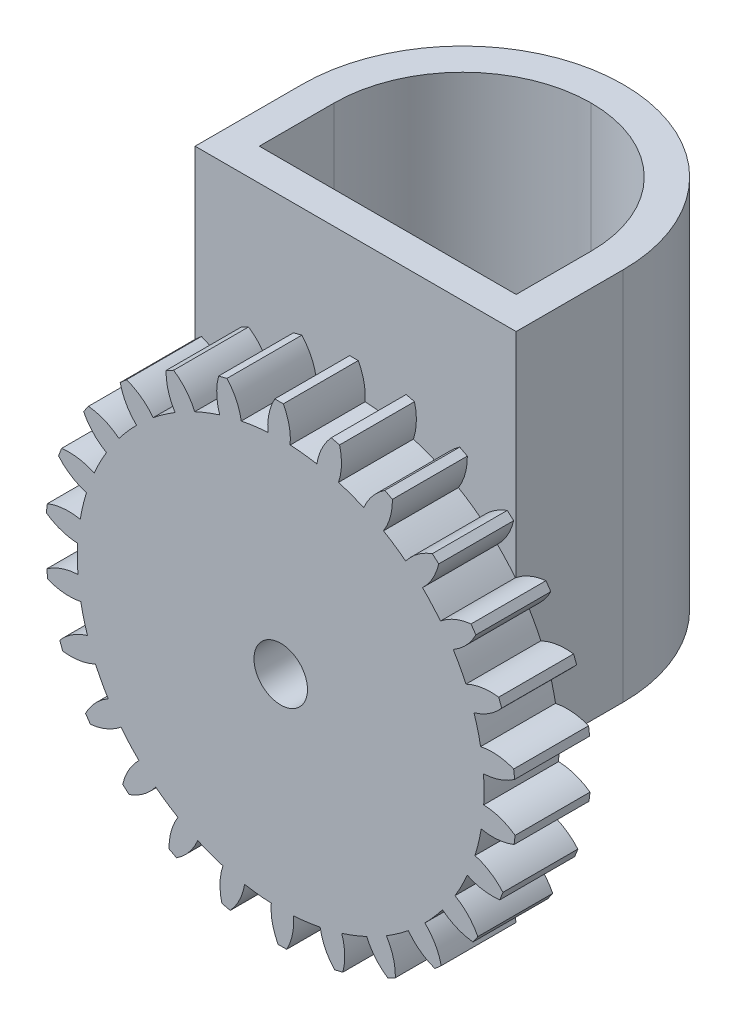
SolidWorks part; units mm, degrees
note: The reader was unsure of these and kept them because the rebuilt part matched: shared geometry of "Sketch5<8>".
ref_plane "Front Plane" through (0, 0, 0) normal (0, 0, 1) x (1, 0, 0)
ref_plane "Top Plane" through (0, 0, 0) normal (0, 1, 0) x (1, 0, 0)
ref_plane "Right Plane" through (0, 0, 0) normal (1, 0, 0) x (0, 0, -1)
sketch "Sketch4" plane through (0, 0, 0) normal (0, 1, 0) x (1, 0, 0)
  line L1 (15, 12.5) -> (-15, 12.5)
  line L2 (15, 12.5) -> (15, -12.5)
  line L3 (15, -12.5) -> (-15, -12.5)
  line L4 (-15, 12.5) -> (-15, -12.5)
  line L5 (15, 12.5) -> (-15, -12.5) construction
  line L6 (15, -12.5) -> (-15, 12.5) construction
  point P0 (0, 0)
  dimension "D1" = 25
  dimension "D2" = 30
extrude "Boss-Extrude2" add sketch "Sketch4" against normal blind 35
fillet "Fillet1" radius 15 2 edges at (-15, -17.5, -12.5) (15, -17.5, -12.5)
shell "Shell1" thickness 3
sketch "Sketch5" plane through (0, 0, 12.5) normal (0, 0, 1) x (1, 0, 0)
  line L1 (-0.2425, -53.7182) -> (0.5575, -53.7182)
  line L2 (0, -50.7232) -> (1.197, -50.6854)
  circle A1 centre (0, -31.7232) radius 19
  arc A3 (0.5575, -53.7182) -> (1.197, -50.6854) centre (-4.1843, -51.1345) ccw
  arc A4 (-0.2425, -53.7182) -> (-0.882, -50.6854) centre (4.4993, -51.1345) cw
  dimension "D2" = 38
extrude "Boss-Extrude5" add sketch "Sketch5" along normal blind 7 contours A1
extrude "Boss-Extrude6" add sketch "Sketch5<8>" along normal blind 7
sketch "Sketch5<8>" plane through (0, 0, 12.5) normal (0, 0, 1) x (1, 0, 0) same geometry as "Sketch5"
pattern_circular "CirPattern1" count 26 over 360 about axis through (0, -31.7232, 0) along (0, 0, 1) of "Boss-Extrude6"
sketch "Sketch6" plane through (0, 0, 19.5) normal (0, 0, 1) x (1, 0, 0)
  circle A0 centre (0, -31.7232) radius 2.5
  dimension "D1" = 5
extrude "Cut-Extrude1" cut sketch "Sketch6" against normal blind 7
